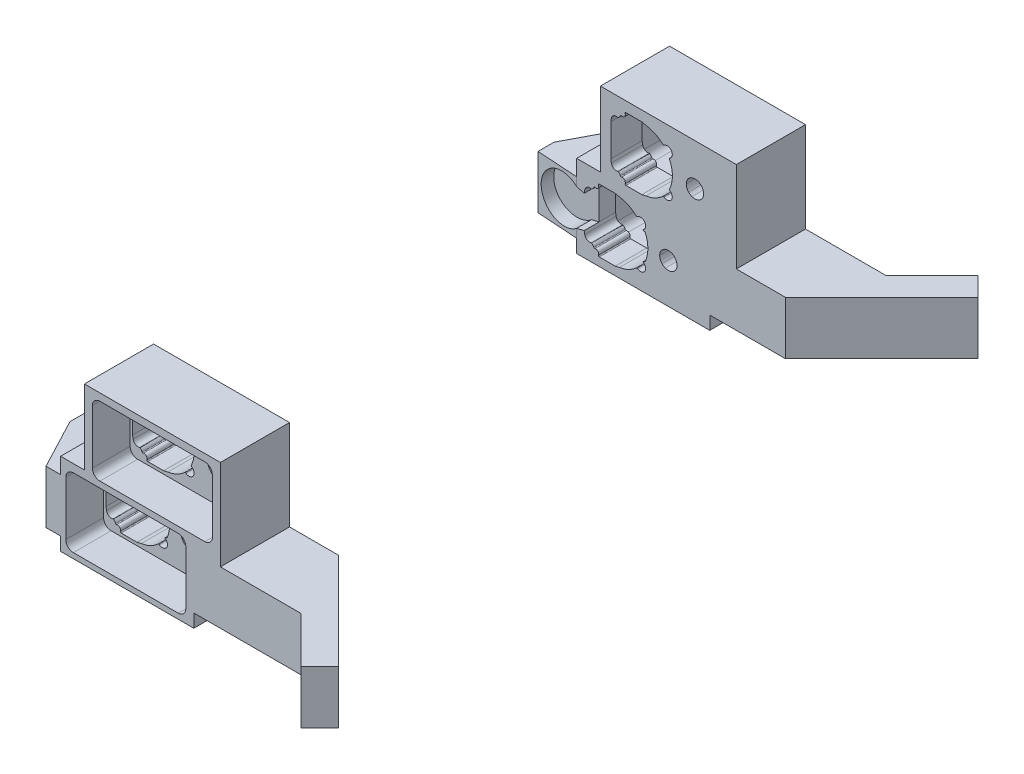
SolidWorks part; units mm, degrees
note: The reader was unsure of these and kept them because the rebuilt part matched: shared geometry of "Sketch5<3>", "Sketch5<4>".
ref_plane "Front Plane" through (0, 0, 0) normal (0, 0, 1) x (1, 0, 0)
ref_plane "Top Plane" through (0, 0, 0) normal (0, 1, 0) x (1, 0, 0)
ref_plane "Right Plane" through (0, 0, 0) normal (1, 0, 0) x (0, 0, -1)
sketch "Sketch2" plane through (0, 0, 0) normal (0, 1, 0) x (1, 0, 0)
  line L0 (0, 0) -> (269.0165, 0)
  line L1 (0, 0) -> (-341.2497, -341.2497)
  line L2 (0, 0) -> (341.2497, -341.2497)
  line L3 (341.2497, -341.2497) -> (0, -682.4995)
  line L4 (-341.2497, -341.2497) -> (0, -682.4995)
  line L5 (-8.9803, -8.9803) -> (332.2695, -350.23)
  line L6 (-41.275, -60.96) -> (41.275, -60.96)
  line L7 (-41.275, -60.96) -> (-41.275, -86.36)
  line L8 (-41.275, -86.36) -> (41.275, -86.36)
  line L9 (41.275, -60.96) -> (41.275, -86.36)
  line L10 (-41.275, -60.96) -> (41.275, -86.36) construction
  line L11 (-41.275, -86.36) -> (41.275, -60.96) construction
  line L12 (35.3795, -53.34) -> (-12.7, -53.34)
  line L13 (-12.7, -53.34) -> (-12.7, -40.64)
  line L14 (-12.7, -40.64) -> (40.64, -40.64)
  line L15 (43.18, -61.1405) -> (43.18, -87.63)
  line L16 (43.18, -87.63) -> (16.51, -87.63)
  line L17 (16.51, -87.63) -> (16.51, -90.17)
  line L18 (16.51, -90.17) -> (90.17, -90.17)
  line L19 (45.72, -90.17) -> (45.72, -106.68)
  line L20 (6.35, -90.424) -> (44.45, -90.424)
  line L21 (6.35, -90.424) -> (6.35, -100.076)
  line L22 (6.35, -100.076) -> (44.45, -100.076)
  line L23 (44.45, -90.424) -> (44.45, -100.076)
  line L24 (6.35, -90.424) -> (44.45, -100.076) construction
  line L25 (6.35, -100.076) -> (44.45, -90.424) construction
  line L26 (-6.35, -88.9) -> (6.35, -88.9)
  line L27 (-6.35, -88.9) -> (-6.35, -101.6)
  line L28 (-6.35, -101.6) -> (6.35, -101.6)
  line L29 (6.35, -88.9) -> (6.35, -101.6)
  line L30 (-6.35, -88.9) -> (6.35, -101.6) construction
  line L31 (-6.35, -101.6) -> (6.35, -88.9) construction
  line L32 (45.72, -106.68) -> (106.68, -106.68)
  line L33 (6.985, -107.95) -> (-12.7, -107.95)
  line L34 (-12.7, -139.7) -> (121.7395, -139.7)
  line L35 (6.985, -107.95) -> (6.985, -106.68)
  line L36 (6.985, -106.68) -> (45.72, -106.68)
  line L37 (-12.7, -107.95) -> (-12.7, -139.7)
  line L38 (12.7, -53.34) -> (12.7, -59.055)
  line L39 (121.7395, -139.7) -> (143.6841, -161.6446)
  line L40 (143.6841, -161.6446) -> (152.6644, -152.6644)
  line L41 (12.7, -59.055) -> (41.0945, -59.055)
  line L42 (-12.7, -115.57) -> (0, -139.7)
  line L43 (6.985, -106.68) -> (-12.7, -107.95)
  point P5 (0, -73.66)
  point P19 (25.4, -95.25)
  point P27 (0, -95.25)
  point P33 (16.51, -88.9)
  point P48 (88.7195, -106.68)
  dimension "D1" = 482.6
  dimension "D2" = 482.6
  dimension "D3" = 45
  dimension "D4" = 25.4
  dimension "D5" = 82.55
  dimension "D6" = 73.66
  dimension "D7" = 12.7
  dimension "D8" = 12.7
  dimension "D9" = 7.62
  dimension "D10" = 1.905
  dimension "D11" = 1.27
  dimension "D12" = 2.54
  dimension "D13" = 12.7
  dimension "D14" = 12.7
  dimension "D15" = 12.7
  dimension "D16" = 9.652
  dimension "D17" = 9.906
  dimension "D18" = 38.1
  dimension "D19" = 21.59
  dimension "D20" = 25.4
  dimension "D21" = 8.89
  dimension "D22" = 1.27
  dimension "D23" = 16.51
  dimension "D24" = 1.27
  dimension "D25" = 0.635
  dimension "D26" = 12.7
  dimension "D27" = 31.75
  dimension "D28" = 215.9
  dimension "D29" = 1.905
  dimension "D30" = 12.7
  dimension "D31" = 7.62
  dimension "D32" = 12.7
extrude "Boss-Extrude1" add sketch "Sketch2" along normal blind 25.4 contours L37 L42 L34 L5 L32 L36 L35 L33 | L5 L40 L2 L32 | L35 L43 L33
ref_plane "Plane1" through (0, 0, 106.68) normal (0, 0, -1) x (-1, 0, 0)
sketch "Sketch3" plane through (0, 0, 106.68) normal (0, 0, -1) x (-1, 0, 0)
  line L1 (-6.985, 0) -> (12.7, 0) construction
  line L2 (12.7, 25.4) -> (12.7, 0) construction
  circle A0 centre (0, 12.7) radius 11.1125
  dimension "D1" = 22.225
  dimension "D2" = 12.7
  dimension "D3" = 12.7
sketch "Sketch5" plane through (0, 0, 106.68) normal (0, 0, -1) x (-1, 0, 0)
  line L0 (-66.75, 25.6) -> (-66.75, -0.2)
  line L1 (-63.15, -3.8) -> (-13.05, -3.8)
  line L2 (-9.45, -0.2) -> (-9.45, 25.6)
  line L3 (-13.05, 29.2) -> (-63.15, 29.2)
  line L4 (-10.6112, 20.4467) -> (-10.8742, 21.9383)
  line L5 (-10.6051, 5.0227) -> (-10.6051, 20.3773)
  line L6 (-10.8742, 3.4617) -> (-10.6112, 4.9533)
  line L7 (-25.3918, -2.3449) -> (-17.8279, -2.3449)
  line L8 (-27.4594, -1.8827) -> (-25.4809, -2.3348)
  line L9 (-36.1085, 1.9194) -> (-35.9287, 2.05)
  line L10 (-38.7, 6.0374) -> (-38.9621, 5.847)
  line L11 (-38.9621, 19.553) -> (-38.7, 19.3626)
  line L12 (-35.9287, 23.35) -> (-36.1085, 23.4806)
  line L13 (-25.4809, 27.7348) -> (-27.4594, 27.2827)
  line L14 (-17.8279, 27.7449) -> (-25.3918, 27.7449)
  line L15 (-6.985, 0) -> (-106.68, 0) construction
  line L16 (-79.45, 61.521) -> (-79.45, 35.721)
  line L17 (-75.85, 32.121) -> (-25.75, 32.121)
  line L18 (-22.15, 35.721) -> (-22.15, 61.521)
  line L19 (-25.75, 65.121) -> (-75.85, 65.121)
  line L20 (-23.3112, 56.3678) -> (-23.5742, 57.8593)
  line L21 (-23.3051, 40.9437) -> (-23.3051, 56.2983)
  line L22 (-23.5742, 39.3827) -> (-23.3112, 40.8743)
  line L23 (-38.0918, 33.5761) -> (-30.5279, 33.5761)
  line L24 (-40.1594, 34.0383) -> (-38.1809, 33.5862)
  line L25 (-48.8085, 37.8404) -> (-48.6287, 37.971)
  line L26 (-51.4, 41.9584) -> (-51.6621, 41.7681)
  line L27 (-51.6621, 55.474) -> (-51.4, 55.2836)
  line L28 (-48.6287, 59.271) -> (-48.8085, 59.4016)
  line L29 (-38.1809, 63.6558) -> (-40.1594, 63.2037)
  line L30 (-30.5279, 63.6659) -> (-38.0918, 63.6659)
  arc A0 (-49.3655, 16.5858) -> (-49.3655, 8.8142) centre (-50.8, 12.7) ccw
  arc A1 (-63.15, 29.2) -> (-66.75, 25.6) centre (-63.15, 25.6) ccw
  arc A2 (-66.75, -0.2) -> (-63.15, -3.8) centre (-63.15, -0.2) ccw
  arc A3 (-13.05, -3.8) -> (-9.45, -0.2) centre (-13.05, -0.2) ccw
  arc A4 (-9.45, 25.6) -> (-13.05, 29.2) centre (-13.05, 25.6) ccw
  circle A5 centre (-52.4, 12.7) radius 6.114
  arc A6 (-15.2144, 25.1458) -> (-14.1814, 23.8887) centre (-12.65, 26.2) ccw
  arc A7 (-10.8742, 21.9383) -> (-13.9331, 23.8504) centre (-13.2647, 21.5168) ccw
  arc A8 (-10.6051, 20.3773) -> (-10.6112, 20.4467) centre (-11.0051, 20.3773) ccw
  arc A9 (-10.6112, 4.9533) -> (-10.6051, 5.0227) centre (-11.0051, 5.0227) ccw
  arc A10 (-13.9331, 1.5496) -> (-10.8742, 3.4617) centre (-13.2647, 3.8832) ccw
  arc A11 (-14.1814, 1.5113) -> (-15.2144, 0.2542) centre (-12.65, -0.8) ccw
  arc A12 (-15.7102, 0.0266) -> (-17.4545, -1.8014) centre (-16.15, -1.3) ccw
  arc A13 (-25.4809, -2.3348) -> (-25.3918, -2.3449) centre (-25.3918, -1.9449) ccw
  arc A14 (-35.5457, 2.0247) -> (-27.4594, -1.8827) centre (-25.4, 12.7) ccw
  arc A15 (-38.9621, 5.847) -> (-36.1085, 1.9194) centre (-37.5353, 3.8832) ccw
  arc A16 (-39.6713, 18.9909) -> (-39.6713, 6.4091) centre (-25.4, 12.7) ccw
  arc A17 (-36.1085, 23.4806) -> (-38.9621, 19.553) centre (-37.5353, 21.5168) ccw
  arc A18 (-27.4594, 27.2827) -> (-35.5457, 23.3753) centre (-25.4, 12.7) ccw
  arc A19 (-25.3918, 27.7449) -> (-25.4809, 27.7348) centre (-25.3918, 27.3449) ccw
  arc A20 (-17.4545, 27.2014) -> (-15.7102, 25.3734) centre (-16.15, 26.7) ccw
  arc A21 (-62.0655, 52.5068) -> (-62.0655, 44.7352) centre (-63.5, 48.621) ccw
  arc A22 (-75.85, 65.121) -> (-79.45, 61.521) centre (-75.85, 61.521) ccw
  arc A23 (-79.45, 35.721) -> (-75.85, 32.121) centre (-75.85, 35.721) ccw
  arc A24 (-25.75, 32.121) -> (-22.15, 35.721) centre (-25.75, 35.721) ccw
  arc A25 (-22.15, 61.521) -> (-25.75, 65.121) centre (-25.75, 61.521) ccw
  circle A26 centre (-65.1, 48.621) radius 6.114
  arc A27 (-27.9144, 61.0669) -> (-26.8814, 59.8097) centre (-25.35, 62.121) ccw
  arc A28 (-23.5742, 57.8593) -> (-26.6331, 59.7714) centre (-25.9647, 57.4378) ccw
  arc A29 (-23.3051, 56.2983) -> (-23.3112, 56.3678) centre (-23.7051, 56.2983) ccw
  arc A30 (-23.3112, 40.8743) -> (-23.3051, 40.9437) centre (-23.7051, 40.9437) ccw
  arc A31 (-26.6331, 37.4706) -> (-23.5742, 39.3827) centre (-25.9647, 39.8042) ccw
  arc A32 (-26.8814, 37.4323) -> (-27.9144, 36.1752) centre (-25.35, 35.121) ccw
  arc A33 (-28.4102, 35.9476) -> (-30.1545, 34.1196) centre (-28.85, 34.621) ccw
  arc A34 (-38.1809, 33.5862) -> (-38.0918, 33.5761) centre (-38.0918, 33.9761) ccw
  arc A35 (-48.2457, 37.9458) -> (-40.1594, 34.0383) centre (-38.1, 48.621) ccw
  arc A36 (-51.6621, 41.7681) -> (-48.8085, 37.8404) centre (-50.2353, 39.8042) ccw
  arc A37 (-51.3055, 54.9119) -> (-51.3055, 42.3301) centre (-38.1, 48.621) ccw
  arc A38 (-48.8085, 59.4016) -> (-51.6621, 55.474) centre (-50.2353, 57.4378) ccw
  arc A39 (-40.1594, 63.2037) -> (-48.2457, 59.2963) centre (-38.1, 48.621) ccw
  arc A40 (-38.0918, 63.6659) -> (-38.1809, 63.6558) centre (-38.0918, 63.2659) ccw
  arc A41 (-30.1545, 63.1224) -> (-28.4102, 61.2945) centre (-28.85, 62.621) ccw
  spline S0 degree 3 poles (-47.782, 15.5405) (-47.8302, 15.5901) (-47.9247, 15.6873) (-48.0726, 15.8214) (-48.22, 15.9439) (-48.3667, 16.0548) (-48.5567, 16.1861) (-48.7933, 16.3285) (-49.0779, 16.4727) (-49.2712, 16.5487) (-49.3655, 16.5858) knots 0 0 0 0 0.10878 0.213334 0.313673 0.409805 0.501742 0.675683 0.841732 1 1 1 1
  spline S1 degree 3 poles (-49.3655, 8.8142) (-49.309, 8.8358) (-49.1943, 8.8798) (-49.0238, 8.9564) (-48.852, 9.0425) (-48.6797, 9.1393) (-48.4829, 9.2626) (-48.2613, 9.4212) (-48.0157, 9.6236) (-47.8616, 9.7791) (-47.782, 9.8595) knots 0 0 0 0 0.094499 0.191816 0.291979 0.395011 0.500935 0.655694 0.822034 1 1 1 1
  spline S2 degree 3 poles (-47.782, 9.8595) (-47.736, 9.9095) (-47.6428, 10.011) (-47.5105, 10.1747) (-47.3824, 10.3498) (-47.2604, 10.5371) (-47.1455, 10.7366) (-47.039, 10.9482) (-46.9218, 11.2193) (-46.8086, 11.5494) (-46.7176, 11.9356) (-46.6623, 12.3193) (-46.6555, 12.5742) (-46.6522, 12.7) knots 0 0 0 0 0.065343 0.132731 0.202172 0.273671 0.347234 0.422865 0.500569 0.630039 0.756419 0.879731 1 1 1 1
  spline S3 degree 3 poles (-46.6522, 12.7) (-46.653, 12.7626) (-46.6547, 12.8885) (-46.6682, 13.0783) (-46.6901, 13.2695) (-46.7215, 13.4619) (-46.7624, 13.6549) (-46.8131, 13.848) (-46.8738, 14.0407) (-46.9696, 14.2994) (-47.1124, 14.611) (-47.3155, 14.957) (-47.5368, 15.2676) (-47.7017, 15.4512) (-47.782, 15.5405) knots 0 0 0 0 0.05983 0.12042 0.181774 0.243895 0.306785 0.370449 0.434888 0.500106 0.634538 0.762645 0.884456 1 1 1 1
  spline S4 degree 3 poles (-15.2144, 25.1458) (-15.2527, 25.2392) (-15.3267, 25.3157) (-15.5084, 25.399) (-15.6144, 25.4052) (-15.7102, 25.3734) knots 0 0 0 0 0.000302 0.000302 0.000604 0.000604 0.000604 0.000604 weights 1 1 1 1 1 1
  spline S5 degree 3 poles (-13.9331, 23.8504) (-14.0168, 23.8264) (-14.1087, 23.8406) (-14.1814, 23.8887) knots 0 0 0 0 0.000258 0.000258 0.000258 0.000258 weights 1 1 1 1
  spline S6 degree 3 poles (-14.1814, 1.5113) (-14.1087, 1.5594) (-14.0168, 1.5736) (-13.9331, 1.5496) knots 0 0 0 0 0.000258 0.000258 0.000258 0.000258 weights 1 1 1 1
  spline S7 degree 3 poles (-15.7102, 0.0266) (-15.6144, -0.0052) (-15.5082, 0.001) (-15.3265, 0.0845) (-15.2527, 0.1608) (-15.2144, 0.2542) knots 0 0 0 0 0.000302 0.000302 0.000604 0.000604 0.000604 0.000604 weights 1 1 1 1 1 1
  spline S8 degree 3 poles (-17.8279, -2.3449) (-17.6976, -2.3449) (-17.5713, -2.2779) (-17.4248, -2.0643) (-17.4078, -1.9231) (-17.4545, -1.8014) knots 0 0 0 0 0.000388 0.000388 0.000776 0.000776 0.000776 0.000776 weights 1 1 1 1 1 1
  spline S9 degree 3 poles (-35.9287, 2.05) (-35.872, 2.0912) (-35.8026, 2.1112) (-35.6631, 2.1021) (-35.5966, 2.073) (-35.5457, 2.0247) knots 0 0 0 0 0.000207 0.000207 0.000415 0.000415 0.000415 0.000415 weights 1 1 1 1 1 1
  spline S10 degree 3 poles (-39.6713, 6.4091) (-39.4915, 6.4703) (-39.2959, 6.4665) (-38.942, 6.3313) (-38.7931, 6.203) (-38.7, 6.0374) knots 0 0 0 0 0.000207 0.000207 0.000414 0.000414 0.000414 0.000414 weights 1 1 1 1 1 1
  spline S11 degree 3 poles (-38.7, 19.3626) (-38.7931, 19.197) (-38.9412, 19.0692) (-39.2949, 18.9336) (-39.4915, 18.9297) (-39.6713, 18.9909) knots 0 0 0 0 0.000207 0.000207 0.000414 0.000414 0.000414 0.000414 weights 1 1 1 1 1 1
  spline S12 degree 3 poles (-35.5457, 23.3753) (-35.5966, 23.327) (-35.6627, 23.298) (-35.8022, 23.2887) (-35.872, 23.3088) (-35.9287, 23.35) knots 0 0 0 0 0.000207 0.000207 0.000415 0.000415 0.000415 0.000415 weights 1 1 1 1 1 1
  spline S13 degree 3 poles (-17.4545, 27.2014) (-17.4078, 27.3231) (-17.425, 27.465) (-17.5718, 27.6783) (-17.6976, 27.7449) (-17.8279, 27.7449) knots 0 0 0 0 0.000388 0.000388 0.000776 0.000776 0.000776 0.000776 weights 1 1 1 1 1 1
  spline S14 degree 3 poles (-60.482, 51.4615) (-60.5302, 51.5111) (-60.6247, 51.6083) (-60.7726, 51.7424) (-60.92, 51.865) (-61.0667, 51.9758) (-61.2567, 52.1071) (-61.4933, 52.2495) (-61.7779, 52.3937) (-61.9712, 52.4697) (-62.0655, 52.5068) knots 0 0 0 0 0.10878 0.213334 0.313673 0.409805 0.501742 0.675683 0.841732 1 1 1 1
  spline S15 degree 3 poles (-62.0655, 44.7352) (-62.009, 44.7569) (-61.8943, 44.8008) (-61.7238, 44.8774) (-61.552, 44.9635) (-61.3797, 45.0603) (-61.1829, 45.1836) (-60.9613, 45.3422) (-60.7157, 45.5446) (-60.5616, 45.7001) (-60.482, 45.7805) knots 0 0 0 0 0.094499 0.191816 0.291979 0.395011 0.500935 0.655694 0.822034 1 1 1 1
  spline S16 degree 3 poles (-60.482, 45.7805) (-60.436, 45.8305) (-60.3428, 45.932) (-60.2105, 46.0957) (-60.0824, 46.2708) (-59.9604, 46.4582) (-59.8455, 46.6576) (-59.739, 46.8692) (-59.6218, 47.1403) (-59.5086, 47.4705) (-59.4176, 47.8566) (-59.3623, 48.2403) (-59.3555, 48.4952) (-59.3522, 48.621) knots 0 0 0 0 0.065343 0.132731 0.202172 0.273671 0.347234 0.422865 0.500569 0.630039 0.756419 0.879731 1 1 1 1
  spline S17 degree 3 poles (-59.3522, 48.621) (-59.353, 48.6836) (-59.3547, 48.8096) (-59.3682, 48.9993) (-59.3901, 49.1906) (-59.4215, 49.383) (-59.4624, 49.576) (-59.5131, 49.7691) (-59.5738, 49.9618) (-59.6696, 50.2204) (-59.8124, 50.5321) (-60.0155, 50.878) (-60.2368, 51.1887) (-60.4017, 51.3722) (-60.482, 51.4615) knots 0 0 0 0 0.05983 0.12042 0.181774 0.243895 0.306785 0.370449 0.434888 0.500106 0.634538 0.762645 0.884456 1 1 1 1
  spline S18 degree 3 poles (-27.9144, 61.0669) (-27.9527, 61.1602) (-28.0267, 61.2367) (-28.2084, 61.32) (-28.3144, 61.3262) (-28.4102, 61.2945) knots 0 0 0 0 0.000302 0.000302 0.000604 0.000604 0.000604 0.000604 weights 1 1 1 1 1 1
  spline S19 degree 3 poles (-26.6331, 59.7714) (-26.7168, 59.7474) (-26.8087, 59.7616) (-26.8814, 59.8097) knots 0 0 0 0 0.000258 0.000258 0.000258 0.000258 weights 1 1 1 1
  spline S20 degree 3 poles (-26.8814, 37.4323) (-26.8087, 37.4804) (-26.7168, 37.4946) (-26.6331, 37.4706) knots 0 0 0 0 0.000258 0.000258 0.000258 0.000258 weights 1 1 1 1
  spline S21 degree 3 poles (-28.4102, 35.9476) (-28.3144, 35.9158) (-28.2082, 35.9221) (-28.0265, 36.0055) (-27.9527, 36.0818) (-27.9144, 36.1752) knots 0 0 0 0 0.000302 0.000302 0.000604 0.000604 0.000604 0.000604 weights 1 1 1 1 1 1
  spline S22 degree 3 poles (-30.5279, 33.5761) (-30.3976, 33.5761) (-30.2713, 33.6431) (-30.1248, 33.8567) (-30.1078, 33.998) (-30.1545, 34.1196) knots 0 0 0 0 0.000388 0.000388 0.000776 0.000776 0.000776 0.000776 weights 1 1 1 1 1 1
  spline S23 degree 3 poles (-48.6287, 37.971) (-48.572, 38.0122) (-48.5026, 38.0322) (-48.3631, 38.0231) (-48.2966, 37.9941) (-48.2457, 37.9458) knots 0 0 0 0 0.000207 0.000207 0.000415 0.000415 0.000415 0.000415 weights 1 1 1 1 1 1
  spline S24 degree 3 poles (-51.3055, 42.3301) (-51.2754, 42.2669) (-51.2684, 42.1951) (-51.3028, 42.0597) (-51.3434, 41.9996) (-51.4, 41.9584) knots 0 0 0 0 0.000207 0.000207 0.000414 0.000414 0.000414 0.000414 weights 1 1 1 1 1 1
  spline S25 degree 3 poles (-51.4, 55.2836) (-51.3434, 55.2424) (-51.3029, 55.1827) (-51.2684, 55.0473) (-51.2754, 54.9751) (-51.3055, 54.9119) knots 0 0 0 0 0.000207 0.000207 0.000414 0.000414 0.000414 0.000414 weights 1 1 1 1 1 1
  spline S26 degree 3 poles (-48.2457, 59.2963) (-48.2966, 59.248) (-48.3627, 59.219) (-48.5022, 59.2098) (-48.572, 59.2298) (-48.6287, 59.271) knots 0 0 0 0 0.000207 0.000207 0.000415 0.000415 0.000415 0.000415 weights 1 1 1 1 1 1
  spline S27 degree 3 poles (-30.1545, 63.1224) (-30.1078, 63.2441) (-30.125, 63.386) (-30.2718, 63.5994) (-30.3976, 63.6659) (-30.5279, 63.6659) knots 0 0 0 0 0.000388 0.000388 0.000776 0.000776 0.000776 0.000776 weights 1 1 1 1 1 1
  dimension "D1" = 1.6
  dimension "D2" = 25.4
  dimension "D3" = 15.95
  dimension "D4" = 16.5
  dimension "D5" = 12.7
  dimension "D6" = 1.6
  dimension "D7" = 25.4
  dimension "D8" = 15.95
  dimension "D9" = 16.5
  dimension "D10" = 38.1
  dimension "D11" = 12.7
sketch "Sketch6" plane through (0, 0, 0) normal (0, -1, 0) x (1, 0, 0)
  line L0 (0, 139.7) -> (121.7395, 139.7) construction
  line L1 (6.985, 106.68) -> (106.68, 106.68)
  line L2 (6.985, 106.68) -> (6.985, 139.7)
  line L3 (6.985, 139.7) -> (106.68, 139.7)
  line L4 (106.68, 106.68) -> (106.68, 139.7)
  point P7 (0, 0)
extrude "Boss-Extrude2" add sketch "Sketch6" along normal blind 6.35 and the other way offset from surface (68.58 mm away) 43.18 contours L2 L3 L4 L1 other way up to face at (63.2941, 25.4, 128.8236)
extrude "Cut-Extrude2" cut sketch "Sketch5" along normal blind 18.034 from surface at -33.02 contours L19 A22 L16 A23 L17 A24 L18 A25 | L3 A1 L0 A2 L1 A3 L2 A4 starting at face at (58.1782, 18.8383, 139.7)
extrude "Cut-Extrude3" cut sketch "Sketch3" against normal blind 7.1628
extrude "Cut-Extrude4" cut sketch "Sketch5<3>" against normal up to next contours A20 S13 L14 A19 L13 A18 S12 L12 A17 L11 S11 A16 S10 L10 A15 L9 S9 A14 L8 A13 L7 S8 A12 S7 A11 S6 A10 L6 A9 L5 A8 L4 A7 S5 A6 S4 | S16 S17 S14 A21 S15 | A41 S27 L30 A40 L29 A39 S26 L28 A38 L27 S25 A37 S24 L26 A36 L25 S23 A35 L24 A34 L23 S22 A33 S21 A32 S20 A31 L22 A30 L21 A29 L20 A28 S19 A27 S18 | A0 S1 S2 S3 S0
sketch "Sketch5<3>" plane through (0, 0, 106.68) normal (0, 0, -1) x (-1, 0, 0) same geometry as "Sketch5"
extrude "Cut-Extrude5" cut sketch "Sketch5<4>" along normal blind 2.54 from surface at -14.986 contours A5 S3 S2 S1 A0 S0 | A26 starting at face at (50.8, 48.621, 121.666)
sketch "Sketch5<4>" plane through (0, 0, 106.68) normal (0, 0, -1) x (-1, 0, 0) same geometry as "Sketch5"
sketch "Sketch7" plane through (0, 0, 106.68) normal (0, 0, -1) x (-1, 0, 0)
  line L0 (-6.985, 21.3428) -> (-10.6051, 20.3773)
  line L1 (-6.985, 4.0572) -> (-10.6112, 4.9533)
  line L3 (-10.6051, 20.3773) -> (-10.6051, 16.0195)
  line L4 (-10.6051, 16.0195) -> (-6.985, 21.3428)
  line L5 (-10.6112, 4.9533) -> (-10.6051, 9.3805)
  line L6 (-10.6051, 9.3805) -> (-6.985, 4.0572)
  arc A0 (-10.6051, 9.3805) -> (-6.985, 4.0572) centre (0, 12.7) ccw construction
  arc A1 (-6.985, 21.3428) -> (-10.6051, 16.0195) centre (0, 12.7) ccw construction
extrude "Cut-Extrude6" cut sketch "Sketch7" against normal up to surface (7.1628 mm away) up to face at (-0.2537, 12.7, 113.8428)
ref_plane "Plane2" through (0, 0, 106.68) normal (0, 0, -1) x (-1, 0, 0)
sketch "Sketch8" plane through (0, 0, 106.68) normal (0, 0, -1) x (-1, 0, 0)
  line L0 (-83.26, 68.58) -> (-83.26, 25.4)
  line L1 (-6.985, 68.58) -> (-106.68, 68.58) construction
  line L2 (-106.68, 25.4) -> (-83.26, 25.4)
  line L3 (-79.45, 61.521) -> (-79.45, 35.721) construction
  line L4 (-18.34, 68.58) -> (-18.34, 33.01)
  line L8 (-106.68, 0) -> (-70.56, 0)
  line L9 (-70.56, 0) -> (-70.56, -6.35)
  line L10 (-6.985, -6.35) -> (-106.68, -6.35) construction
  line L11 (-66.75, 25.6) -> (-66.75, -0.2) construction
  line L12 (-18.34, 33.01) -> (-6.985, 33.01)
  line L14 (-22.15, 35.721) -> (-22.15, 61.521) construction
  line L15 (-13.05, 29.2) -> (-63.15, 29.2) construction
  line L16 (-106.68, 0) -> (-106.68, -6.35)
  line L17 (-106.68, -6.35) -> (-70.56, -6.35)
  line L18 (-106.68, 25.4) -> (-106.68, 68.58)
  line L19 (-106.68, 68.58) -> (-83.26, 68.58)
  line L22 (-18.34, 68.58) -> (-6.985, 68.58)
  line L23 (-6.985, 68.58) -> (-6.985, 33.01)
  dimension "D1" = 3.81
  dimension "D2" = 90
  dimension "D3" = 3.81
  dimension "D4" = 3.81
  dimension "D5" = 3.81
extrude "Cut-Extrude7" cut sketch "Sketch8" against normal up to next
mirror "Mirror2" about plane through (0, 0, 0) normal (0, 0, 1) of bodies 109
